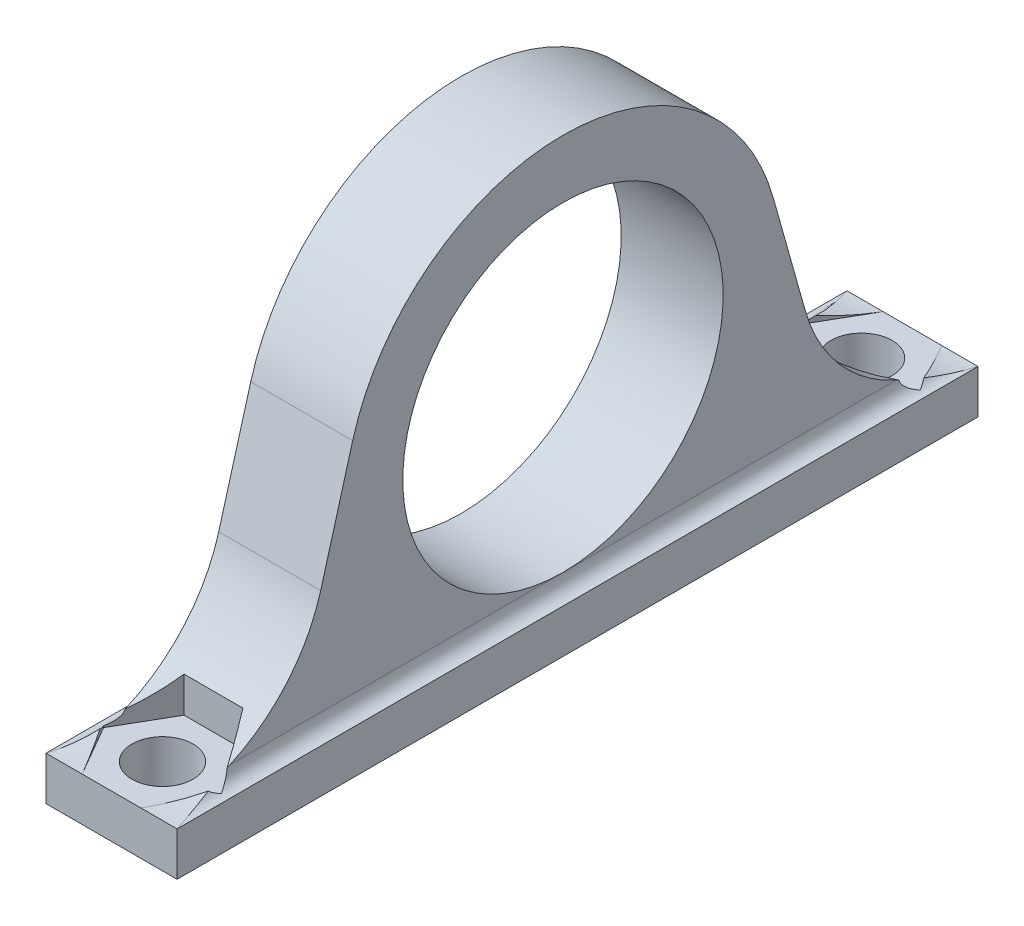
SolidWorks part; units mm, degrees
ref_plane "前基準面" through (0, 0, 0) normal (0, 0, 1) x (1, 0, 0)
ref_plane "上基準面" through (0, 0, 0) normal (0, 1, 0) x (1, 0, 0)
ref_plane "右基準面" through (0, 0, 0) normal (1, 0, 0) x (0, 0, -1)
sketch "草圖1" plane through (0, 0, 0) normal (0, 1, 0) x (1, 0, 0)
  line L1 (-4.5, -27.5) -> (4.5, -27.5)
  line L2 (-4.5, -27.5) -> (-4.5, 27.5)
  line L3 (-4.5, 27.5) -> (4.5, 27.5)
  line L4 (4.5, -27.5) -> (4.5, 27.5)
  line L5 (0, 27.5) -> (0, -27.5) construction
  line L6 (-4.5, 0) -> (4.5, 0) construction
  circle A0 centre (0, 24) radius 2.1
  circle A2 centre (0, -24) radius 2.1
  point P0 (0, 0)
  point P6 (0, -24)
  dimension "D2" = 4.2
  dimension "D3" = 48
  dimension "D4" = 55
  dimension "D5" = 9
extrude "填料-伸長1" add sketch "草圖1" along normal blind 3
sketch "草圖2" plane through (0, 0, 0) normal (1, 0, 0) x (0, 0, -1)
  line L0 (0, -9.6631) -> (0, 9.6631) construction
  line L2 (-14.4401, 19.0601) -> (-18.9557, 3)
  line L3 (-18.9557, 3) -> (18.9557, 3)
  line L4 (14.4401, 19.0601) -> (18.9557, 3)
  line L5 (-27.5, 3) -> (27.5, 3) construction
  circle A0 centre (0, 15) radius 11
  arc A1 (-14.4401, 19.0601) -> (14.4401, 19.0601) centre (0, 15) cw
  point P6 (0, 0)
  point P10 (0, 0)
  point P11 (0, 3)
  point P14 (-18.9557, 3)
  dimension "D1" = 22
  dimension "D2" = 15
  dimension "D3" = 15
extrude "填料-伸長2" add sketch "草圖2" along normal mid plane 7
fillet "圓角1" radius 1 2 edges at (-3.5, 3, 0) (3.5, 3, 0)
fillet "圓角2" radius 11.3 2 edges at (0, 3, -18.9557) (0, 3, 18.9557)
sketch "草圖3" plane through (0, 0, 0) normal (0, -1, 0) x (1, 0, 0)
  line L0 (-38.8482, 0) -> (38.8482, 0) construction
  line L1 (4.0415, -24) -> (2.0207, -20.5)
  line L2 (2.0207, -20.5) -> (-2.0207, -20.5)
  line L3 (-2.0207, -20.5) -> (-4.0415, -24)
  line L4 (-4.0415, -24) -> (-2.0207, -27.5)
  line L5 (-2.0207, -27.5) -> (2.0207, -27.5)
  line L6 (2.0207, -27.5) -> (4.0415, -24)
  line L7 (2.0207, 27.5) -> (4.0415, 24)
  line L8 (-2.0207, 27.5) -> (2.0207, 27.5)
  line L9 (-4.0415, 24) -> (-2.0207, 27.5)
  line L10 (-2.0207, 20.5) -> (-4.0415, 24)
  line L11 (2.0207, 20.5) -> (-2.0207, 20.5)
  line L12 (4.0415, 24) -> (2.0207, 20.5)
  circle A0 centre (0, -24) radius 3.5 construction
  circle A1 centre (0, 24) radius 3.5 construction
  point P13 (0, 0)
  dimension "D1" = 7
extrude "除料-伸長1" cut sketch "草圖3" against normal blind 4 from offset 3 offset against normal yes
